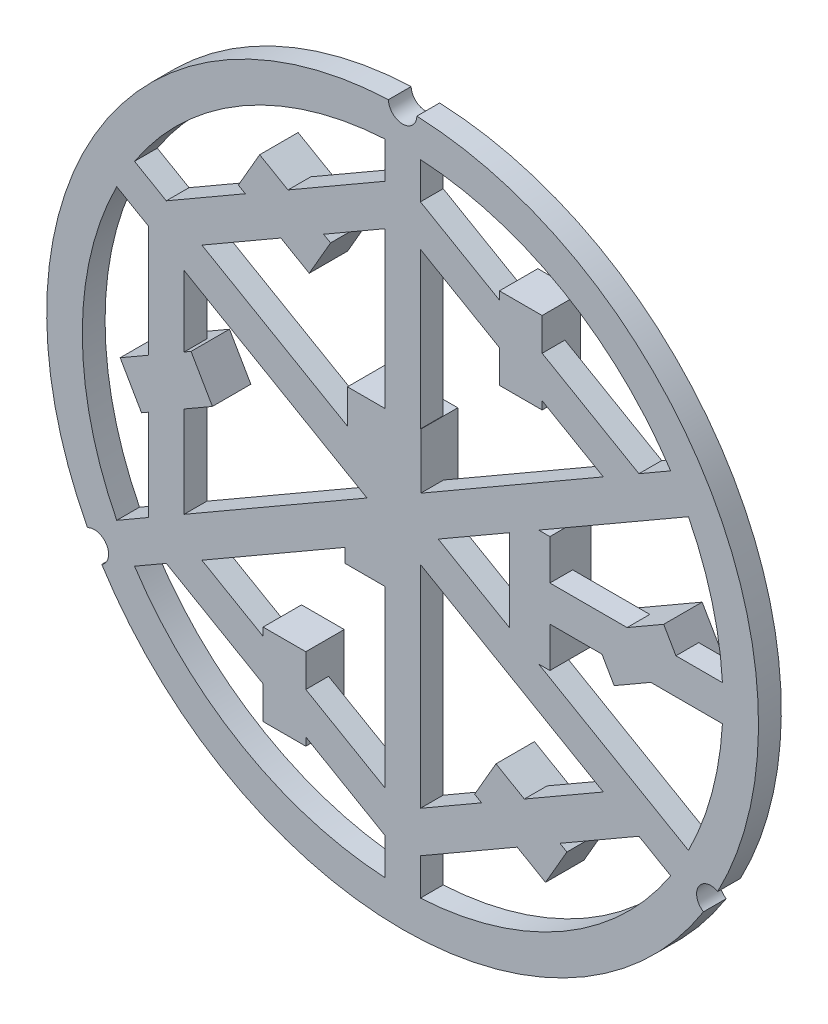
SolidWorks part; units mm, degrees
ref_plane "Front" through (0, 0, 0) normal (0, 0, 1) x (1, 0, 0)
ref_plane "Top" through (0, 0, 0) normal (0, 1, 0) x (1, 0, 0)
ref_plane "Right" through (0, 0, 0) normal (1, 0, 0) x (0, 0, -1)
sketch "Base sketch" plane through (0, 0, 0) normal (0, 0, 1) x (1, 0, 0)
  circle A0 centre (0, 0) radius 25
  dimension "D1" = 50
extrude "Board" add sketch "Base sketch" along normal blind 1.6
hole_wizard "Alignment slots" positions "Sketch3" profile "Sketch2" hole size "Ø2.0" standard "ANSI Metric" end condition through all
sketch "Sketch3" plane through (0, 0, 1.6) normal (0, 0, 1) x (1, 0, 0)
  line L0 (-21.6506, -12.5) -> (0, 0)
  line L1 (0, 0) -> (0, 25)
  line L3 (0, 0) -> (21.6506, -12.5)
  circle A0 centre (0, 0) radius 25 construction
  point P0 (0, 25)
  point P4 (21.6506, -12.5)
  point P6 (-21.6506, -12.5)
  dimension "D1" = 120
  dimension "D2" = 120
sketch "Sketch2" plane through (0, 25, 1.6) normal (1, 0, 0) x (0, -1, 0)
  line L0 (0, 0) -> (0, 1.6)
  line L1 (0, 1.6) -> (1, 1.6)
  line L2 (1, 1.6) -> (1, 0)
  line L5 (1, 0) -> (0, 0)
  line L11 (0, -6.35) -> (0, 107.95) construction
  dimension "Thru Hole Dia." = 2
  dimension "Thru Hole Depth" = 1.6
sketch "Extrusion base" plane through (0, 0, 0) normal (0, 0, -1) x (-1, 0, 0)
  line L0 (10.0398, 17.1126) -> (11.5398, 14.5145)
  line L1 (-1.275, 6.075) -> (3.875, 6.075)
  line L2 (-1.275, 6.075) -> (-1.275, 0.925)
  line L3 (-1.275, 0.925) -> (3.875, 0.925)
  line L4 (3.875, 6.075) -> (3.875, 0.925)
  line L5 (0.95, -1.65) -> (4.05, -1.65)
  line L6 (0.95, -1.65) -> (0.95, -4.75)
  line L7 (0.95, -4.75) -> (4.05, -4.75)
  line L8 (4.05, -1.65) -> (4.05, -4.75)
  line L9 (-10.345, 4.075) -> (-7.495, 4.075)
  line L10 (-10.345, 4.075) -> (-10.345, -4.075)
  line L11 (-10.345, -4.075) -> (-7.495, -4.075)
  line L12 (-7.495, 4.075) -> (-7.495, -4.075)
  line L13 (-9.8, 17.251) -> (-6.8, 17.251)
  line L14 (-9.8, 17.251) -> (-9.8, 11.501)
  line L15 (-9.8, 11.501) -> (-6.8, 11.501)
  line L16 (-6.8, 17.251) -> (-6.8, 11.501)
  line L17 (10.0398, 17.1126) -> (5.0602, 14.2376)
  line L18 (5.0602, 14.2376) -> (6.5602, 11.6395)
  line L19 (11.5398, 14.5145) -> (6.5602, 11.6395)
  line L20 (19.8398, -0.1385) -> (18.3398, -2.7365)
  line L21 (19.8398, -0.1385) -> (14.8602, 2.7365)
  line L22 (14.8602, 2.7365) -> (13.3602, 0.1385)
  line L23 (18.3398, -2.7365) -> (13.3602, 0.1385)
  line L24 (9.8, -17.251) -> (6.8, -17.251)
  line L25 (9.8, -17.251) -> (9.8, -11.501)
  line L26 (9.8, -11.501) -> (6.8, -11.501)
  line L27 (6.8, -17.251) -> (6.8, -11.501)
  line L28 (-10.0398, -17.1126) -> (-11.5398, -14.5145)
  line L29 (-10.0398, -17.1126) -> (-5.0602, -14.2376)
  line L30 (-5.0602, -14.2376) -> (-6.5602, -11.6395)
  line L31 (-11.5398, -14.5145) -> (-6.5602, -11.6395)
  line L32 (-19.8398, 0.1385) -> (-18.3398, 2.7365)
  line L33 (-19.8398, 0.1385) -> (-14.8602, -2.7365)
  line L34 (-14.8602, -2.7365) -> (-13.3602, -0.1385)
  line L35 (-18.3398, 2.7365) -> (-13.3602, -0.1385)
  point P12 (1.3, 0.925)
  point P14 (-1.275, 3.5)
  point P15 (2.5, -1.65)
  point P17 (0.95, -3.2)
  point P18 (-7.495, 0)
  point P22 (-6.8, 14.376)
  point P25 (-8.3, 17.251)
  point P31 (9.05, 13.077)
  point P32 (10.7898, 15.8135)
  point P37 (15.85, -1.299)
  point P38 (19.0898, -1.4375)
  point P43 (6.8, -14.376)
  point P44 (8.3, -17.251)
  point P49 (-9.05, -13.077)
  point P50 (-10.7898, -15.8135)
  point P55 (-15.85, 1.299)
  point P56 (-19.0898, 1.4375)
  point P57 (0, 0)
  dimension "D13" = 5.75
  dimension "D12" = 3
  dimension "D1" = 5.15
  dimension "D2" = 5.15
  dimension "D3" = 3.1
  dimension "D4" = 3.1
  dimension "D5" = 2.85
  dimension "D6" = 8.15
  dimension "D7" = 1.3
  dimension "D8" = 3.5
  dimension "D9" = 2.5
  dimension "D10" = 3.2
  dimension "D11" = 6.22
  dimension "D15" = 8.3
  dimension "D16" = 6
  dimension "D14" = 14.376
extrude "LEDs" add sketch "Extrusion base" along normal blind 1.1 contours L16 L13 L14 L15 | L35 L32 L33 L34 | L31 L28 L29 L30 | L27 L24 L25 L26 | L23 L20 L21 L22 | L19 L0 L17 L18 region at (-8.3, 14.376, 0) region at (8.3, 14.376, 0) region at (-16.6, 0, 0) region at (-8.3, -14.376, 0) region at (8.3, -14.376, 0) region at (16.6, 0, 0)
extrude "ICs" add sketch "Extrusion base<3>" along normal blind 1 contours L4 L1 L2 L3 | L8 L5 L6 L7 region at (-1.3, 3.5, 0) region at (-2.5, -3.2, 0)
sketch "Extrusion base<3>" plane through (0, 0, 0) normal (0, 0, -1) x (-1, 0, 0) same geometry as "Extrusion base"
extrude "Connector" add sketch "Extrusion base<4>" along normal blind 1.3 contours L12 L9 L10 L11 region at (8.92, 0, 0)
sketch "Extrusion base<4>" plane through (0, 0, 0) normal (0, 0, -1) x (-1, 0, 0) same geometry as "Extrusion base"
sketch "Negative base" plane through (0, 0, 0) normal (0, 0, -1) x (-1, 0, 0)
  line L0 (-20.0805, -10.1501) -> (18.8305, 12.3152)
  line L1 (-18.8305, -12.3152) -> (20.0805, 10.1501)
  line L2 (1.25, 22.4653) -> (1.25, -22.4653)
  line L3 (-1.25, 22.4653) -> (-1.25, -22.4653)
  line L4 (18.8305, -12.3152) -> (-20.0805, 10.1501)
  line L5 (20.0805, -10.1501) -> (-18.8305, 12.3152)
  line L6 (-22.4653, 1.25) -> (-10.345, 1.25)
  line L7 (-10.345, 4.075) -> (-7.495, 4.075)
  line L8 (-10.345, 4.075) -> (-10.345, -4.075)
  line L9 (-10.345, -4.075) -> (-7.495, -4.075)
  line L10 (-7.495, 4.075) -> (-7.495, -4.075)
  line L11 (3.875, 0.925) -> (-1.275, 0.925)
  line L12 (3.875, 0.925) -> (3.875, 6.075)
  line L13 (3.875, 6.075) -> (-1.275, 6.075)
  line L14 (-1.275, 0.925) -> (-1.275, 6.075)
  line L15 (0.95, -4.75) -> (4.05, -4.75)
  line L16 (0.95, -4.75) -> (0.95, -1.65)
  line L17 (0.95, -1.65) -> (4.05, -1.65)
  line L18 (4.05, -4.75) -> (4.05, -1.65)
  line L19 (-22.4653, -1.25) -> (-10.345, -1.25)
  line L34 (15.35, -7.419) -> (15.35, 7.419)
  line L35 (17.85, -8.8623) -> (17.85, 8.8623)
  line L36 (1.25, -19.8897) -> (16.6, -11.0274)
  line L37 (1.25, -17.003) -> (14.1, -9.584)
  line L38 (-16.6, -11.0274) -> (-1.25, -19.8897)
  line L39 (-14.1, -9.584) -> (-1.25, -17.003)
  line L42 (16.6, 11.0274) -> (1.25, 19.8897)
  line L43 (14.1, 9.584) -> (1.25, 17.003)
  line L44 (-1.25, 19.8897) -> (-16.6, 11.0274)
  line L45 (-1.25, 17.003) -> (-14.1, 9.584)
  circle A0 centre (0, 0) radius 22.5
  point P18 (0, 0)
  line M1 (-10.345, 4.075) -> (-7.495, 4.075)
  line M2 (-7.495, 4.075) -> (-7.495, -4.075)
  line M3 (-7.495, -4.075) -> (-10.345, -4.075)
  line M4 (-10.345, -4.075) -> (-10.345, 4.075)
  line M6 (4.05, -1.65) -> (4.05, -4.75)
  line M7 (4.05, -4.75) -> (0.95, -4.75)
  line M9 (-1.275, 6.075) -> (3.875, 6.075)
  line M10 (3.875, 6.075) -> (3.875, 0.925)
  line M12 (-1.275, 0.925) -> (-1.275, 6.075)
  line M81 (10.0398, 17.1126) -> (11.5398, 14.5145)
  line M82 (11.5398, 14.5145) -> (6.5602, 11.6395)
  line M83 (6.5602, 11.6395) -> (5.0602, 14.2376)
  line M84 (5.0602, 14.2376) -> (10.0398, 17.1126)
  line M85 (19.8398, -0.1385) -> (18.3398, -2.7365)
  line M86 (18.3398, -2.7365) -> (13.3602, 0.1385)
  line M87 (13.3602, 0.1385) -> (14.8602, 2.7365)
  line M88 (14.8602, 2.7365) -> (19.8398, -0.1385)
  line M89 (9.8, -17.251) -> (6.8, -17.251)
  line M90 (6.8, -17.251) -> (6.8, -11.501)
  line M91 (6.8, -11.501) -> (9.8, -11.501)
  line M92 (9.8, -11.501) -> (9.8, -17.251)
  line M93 (-10.0398, -17.1126) -> (-11.5398, -14.5145)
  line M94 (-11.5398, -14.5145) -> (-6.5602, -11.6395)
  line M95 (-6.5602, -11.6395) -> (-5.0602, -14.2376)
  line M96 (-5.0602, -14.2376) -> (-10.0398, -17.1126)
  line M97 (-19.8398, 0.1385) -> (-18.3398, 2.7365)
  line M98 (-18.3398, 2.7365) -> (-13.3602, -0.1385)
  line M99 (-13.3602, -0.1385) -> (-14.8602, -2.7365)
  line M100 (-14.8602, -2.7365) -> (-19.8398, 0.1385)
  line M101 (-9.8, 17.251) -> (-6.8, 17.251)
  line M102 (-6.8, 17.251) -> (-6.8, 11.501)
  line M103 (-6.8, 11.501) -> (-9.8, 11.501)
  line M104 (-9.8, 11.501) -> (-9.8, 17.251)
  dimension "D1" = 45
  dimension "D2" = 2.5
  dimension "D3" = 1.25
  dimension "D4" = 3
  dimension "D21" = 3
  dimension "D23" = 3
extrude "Extra mass cut" cut sketch "Negative base" against normal through all contours L1 A0 L3 L38 M96 M93 M94 | L1 L39 L3 M94 M95 M96 | L2 L37 L4 M90 M91 M92 M6 M7 | L2 A0 L4 L36 M92 M89 M90 | L5 L34 L1 M86 M87 M88 | L5 A0 L1 L35 M88 M85 M86 | L0 L43 L2 M82 M83 M84 M9 M10 | L0 A0 L2 L42 M84 M81 M82 | L3 L45 L5 M102 M103 M104 M12 M9 | L3 A0 L5 L44 M104 M101 M102 | L4 A0 L6 M97 M98 M4 M1 | L19 A0 L0 M3 M4 M99 M100 | L0 L4 M2 region at (-5.7826, 9.9141, 0) region at (-9.9476, 17.3232, 0) region at (-19.9761, 0.0467, 0) region at (10.0285, 17.2765, 0) region at (5.4215, 9.4614, 0) region at (-10.8974, -0.0365, 0) region at (-10.0285, -17.2765, 0) region at (16.8502, 4.6177, 0) region at (5.83, 0, 0) region at (5.4803, -9.4192, 0) region at (-5.5893, -9.7826, 0) region at (9.9476, -17.3232, 0) region at (16.9348, -4.6177, 0)
